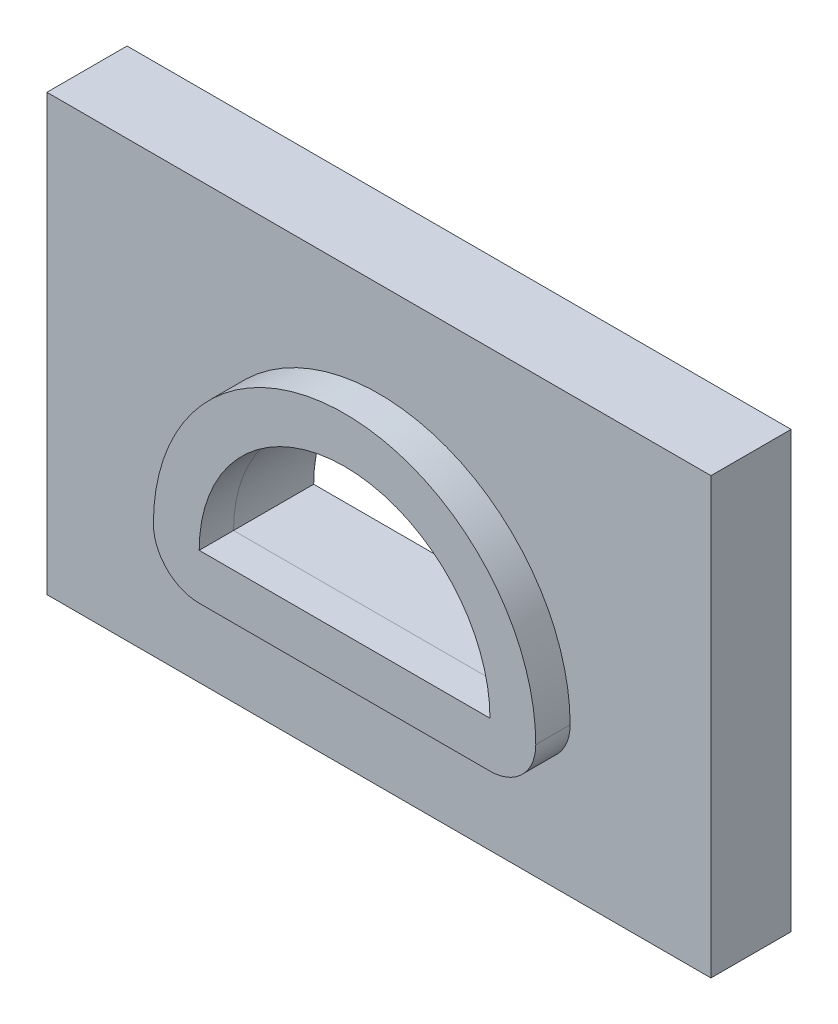
SolidWorks part; units mm, degrees
ref_plane "Front Plane" through (0, 0, 0) normal (0, 0, 1) x (1, 0, 0)
ref_plane "Top Plane" through (0, 0, 0) normal (0, 1, 0) x (1, 0, 0)
ref_plane "Right Plane" through (0, 0, 0) normal (1, 0, 0) x (0, 0, -1)
sketch "Sketch1" plane through (0, 0, 0) normal (0, 0, 1) x (1, 0, 0)
  line L0 (-4.2, 0) -> (8.5, 0)
  line L1 (-6.2, 0) -> (-6.2, -2)
  line L2 (-6.2, -2) -> (10.5, -2)
  line L3 (10.5, -2) -> (10.5, 0)
  line L5 (-12.35, 12.5) -> (16.65, 12.5)
  line L6 (-12.35, 12.5) -> (-12.35, -6.5)
  line L7 (-12.35, -6.5) -> (16.65, -6.5)
  line L8 (16.65, 12.5) -> (16.65, -6.5)
  arc A0 (8.5, 0) -> (-4.2, 0) centre (2.15, 0) ccw
  arc A1 (10.5, 0) -> (-6.2, 0) centre (2.15, 0) ccw
  point P2 (2.15, -6.5)
  dimension "D1" = 12.7
  dimension "D3" = 2
  dimension "D4" = 29
  dimension "D5" = 6.5
  dimension "D7" = 19
  dimension "D2" = 2
extrude "cap alignment lip" add sketch "Sketch1" along normal blind 1.5 contours L3 A1 L1 L2 A0 L0 region at (2.15, 8.1535, 0)
extrude "cap body" add sketch "Sketch1<3>" against normal blind 3.5 separate body contours L8 L5 L6 L7 A1 L3 L2 L1 | L3 A1 L1 L2 A0 L0 region at (2.15, 8.1535, 0) region at (2.15, 12.1533, 0)
sketch "Sketch1<3>" plane through (0, 0, 0) normal (0, 0, 1) x (1, 0, 0) same geometry as "Sketch1"
fillet "lip corner fillet" radius 2 2 edges at (-6.2, -2, 0.75) (10.5, -2, 0.75)
